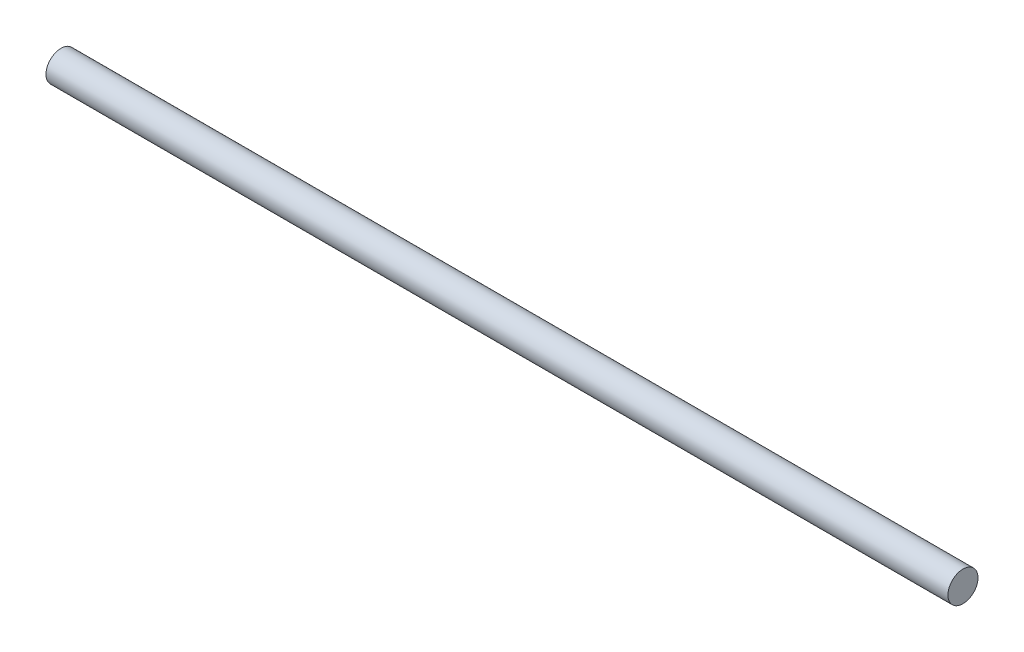
SolidWorks part; units mm, degrees
ref_plane "Front Plane" through (0, 0, 0) normal (0, 0, 1) x (1, 0, 0)
ref_plane "Top Plane" through (0, 0, 0) normal (0, 1, 0) x (1, 0, 0)
ref_plane "Right Plane" through (0, 0, 0) normal (1, 0, 0) x (0, 0, -1)
sketch "Sketch1" plane through (0, 0, 0) normal (1, 0, 0) x (0, 0, -1)
  circle A0 centre (0, 0) radius 2.5
  dimension "D1" = 5
extrude "Boss-Extrude1" add sketch "Sketch1" along normal mid plane 150
